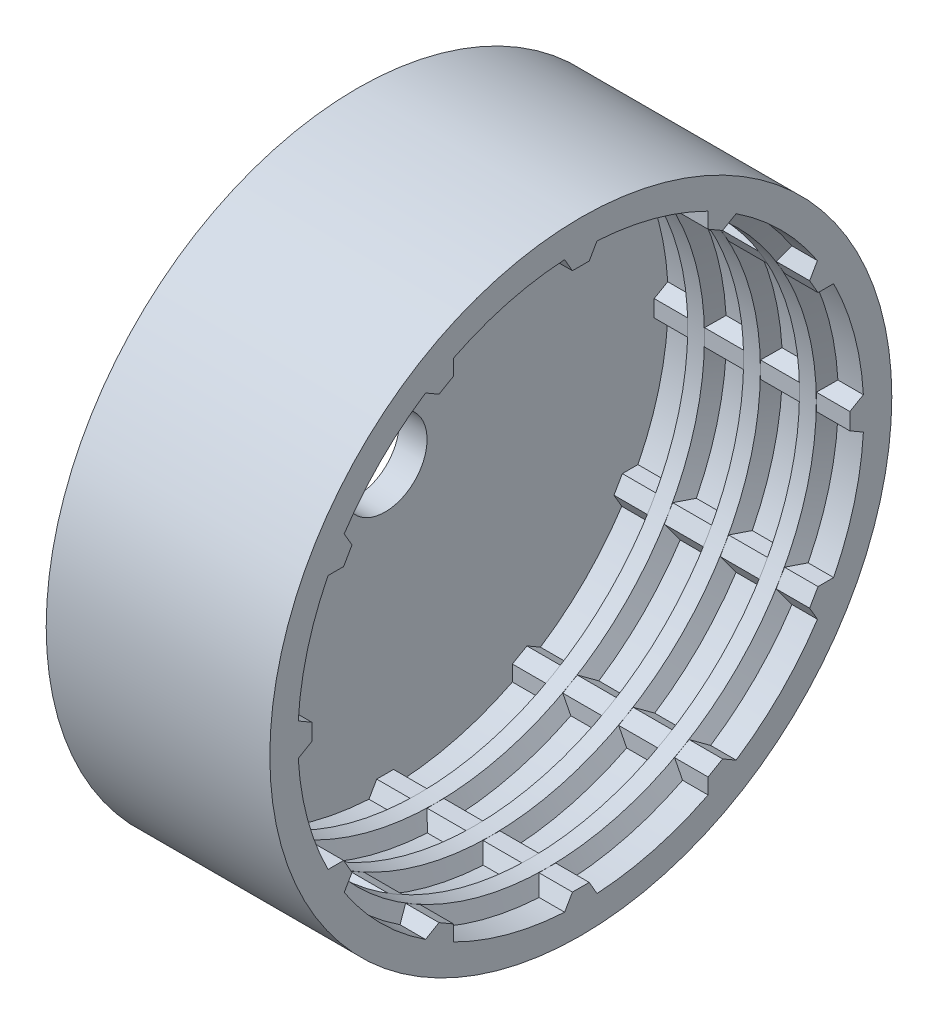
SolidWorks part; units mm, degrees
ref_plane "Front Plane" through (0, 0, 0) normal (0, 0, 1) x (1, 0, 0)
ref_plane "Top Plane" through (0, 0, 0) normal (0, 1, 0) x (1, 0, 0)
ref_plane "Right Plane" through (0, 0, 0) normal (1, 0, 0) x (0, 0, -1)
sketch "Sketch1" plane through (0, 0, 0) normal (0, 1, 0) x (1, 0, 0)
  line L0 (0, 4.7625) -> (0, 35.3219)
  line L1 (0, 35.3219) -> (25.4, 35.3219)
  line L2 (25.4, 35.3219) -> (25.4, 32.1469)
  line L3 (25.4, 32.1469) -> (3.175, 32.1469)
  line L4 (3.175, 32.1469) -> (3.175, 4.7625)
  line L8 (1.5875, 0) -> (24.5079, 0) construction
  line L9 (0, 4.7625) -> (3.175, 4.7625)
  line L15 (13.335, 30.5594) -> (15.24, 30.5594)
  line L16 (15.24, 30.5594) -> (16.1565, 32.1469)
  line L17 (6.985, 30.5594) -> (6.0685, 32.1469)
  line L18 (6.985, 33.7344) -> (8.89, 33.7344)
  line L19 (6.985, 33.7344) -> (6.985, 30.5594)
  line L20 (6.985, 30.5594) -> (8.89, 30.5594)
  line L21 (8.89, 33.7344) -> (8.89, 30.5594)
  line L22 (6.985, 33.7344) -> (8.89, 30.5594) construction
  line L23 (6.985, 30.5594) -> (8.89, 33.7344) construction
  line L28 (13.335, 33.7344) -> (15.24, 30.5594) construction
  line L29 (13.335, 30.5594) -> (12.4185, 32.1469)
  line L30 (8.89, 30.5594) -> (9.8065, 32.1469)
  line L31 (13.335, 33.7344) -> (13.335, 30.5594)
  line L32 (13.335, 30.5594) -> (15.24, 33.7344) construction
  line L33 (13.335, 33.7344) -> (15.24, 33.7344)
  line L34 (15.24, 33.7344) -> (15.24, 30.5594)
  line L35 (19.685, 30.5594) -> (21.59, 30.5594)
  line L36 (21.59, 30.5594) -> (22.5065, 32.1469)
  line L37 (19.685, 33.7344) -> (21.59, 30.5594) construction
  line L38 (19.685, 30.5594) -> (18.7685, 32.1469)
  line L39 (19.685, 33.7344) -> (19.685, 30.5594)
  line L40 (19.685, 30.5594) -> (21.59, 33.7344) construction
  line L41 (19.685, 33.7344) -> (21.59, 33.7344)
  line L42 (21.59, 33.7344) -> (21.59, 30.5594)
  line L43 (6.985, 30.5594) -> (13.335, 30.5594) construction
  point P13 (7.9375, 32.1469)
  dimension "D8" = 4.7625
  dimension "D2" = 64.2938
  dimension "D3" = 3.175
  dimension "D4" = 3.175
  dimension "D5" = 30
  dimension "D6" = 9.525
  dimension "D7" = 1.905
  dimension "D9" = 3.175
  dimension "D10" = 6.35
  dimension "D11" = 3
  dimension "D12" = 22.225
revolve "Revolve1" add sketch "Sketch1" angle 360 about L8 region at (0.3974, 0, -20.0422) region at (6.6795, 0, -31.6177) region at (21.8955, 0, -31.6177) region at (7.9375, 0, -32.9406) region at (7.9375, 0, -31.3531) region at (20.6375, 0, -31.3531) region at (20.6375, 0, -32.9406) region at (9.1955, 0, -31.6177) region at (19.3795, 0, -31.6177) region at (13.0295, 0, -31.6177) region at (15.5455, 0, -31.6177) region at (14.2875, 0, -32.9406) region at (14.2875, 0, -31.3531)
sketch "Sketch2" plane through (3.175, 0, 0) normal (1, 0, 0) x (0, 0, -1)
  line L0 (0, 32.1469) -> (0, 30.5594) construction
  line L1 (-0.9525, 30.5594) -> (0.9525, 30.5594)
  line L2 (-0.9525, 30.5594) -> (-1.8387, 32.0943)
  line L3 (0.9525, 30.5594) -> (1.8387, 32.0943)
  line L4 (-0.9525, 30.5594) -> (-0.9525, 32.1328) construction
  line L5 (0.9525, 30.5594) -> (0.9525, 32.1328) construction
  circle A0 centre (0, 0) radius 32.1469 construction
  arc A6 (-1.8387, 32.0943) -> (1.8387, 32.0943) centre (0, 0) cw
  circle A7 centre (0, 0) radius 30.5594 construction
  point P2 (-0.3651, 28.4356)
  point P3 (0, 32.1469)
  point P8 (0, 0)
  point P9 (0.8404, 32.1359)
  point P12 (0, 30.5594)
  point P15 (-1.048, 32.1298)
  point P16 (0, 32.1469)
  point P19 (1.0164, 28.8552)
  point P20 (0.2169, 32.1461)
  point P21 (0.9525, 28.5315)
  dimension "D1" = 1.905
  dimension "D2" = 30
  dimension "D3" = 30
extrude "Boss-Extrude1" add sketch "Sketch2" along normal up to surface (22.225 mm away) up to face at (25.4, 0, 32.1469)
pattern_circular "CirPattern1" count 12 every 30 about axis through (1.5875, 0, 0) along (-1, 0, 0) of "Boss-Extrude1"
